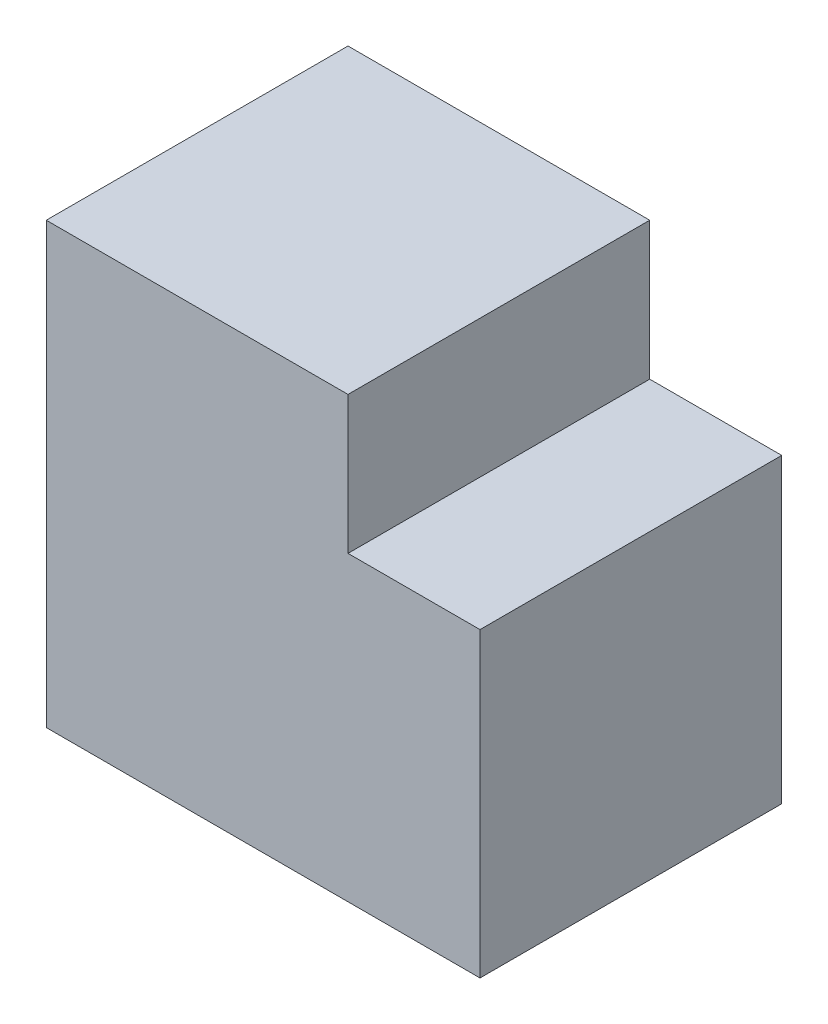
SolidWorks part; units mm, degrees
ref_plane "Front Plane" through (0, 0, 0) normal (0, 0, 1) x (1, 0, 0)
ref_plane "Top Plane" through (0, 0, 0) normal (0, 1, 0) x (1, 0, 0)
ref_plane "Right Plane" through (0, 0, 0) normal (1, 0, 0) x (0, 0, -1)
sketch "Sketch1" plane through (0, 0, 0) normal (0, 1, 0) x (1, 0, 0)
  line L1 (-39.3028, 26.5568) -> (1.3372, 26.5568)
  line L2 (-39.3028, 26.5568) -> (-39.3028, -14.0832)
  line L3 (-39.3028, -14.0832) -> (1.3372, -14.0832)
  line L4 (1.3372, 26.5568) -> (1.3372, -14.0832)
  line L5 (-39.3028, 26.5568) -> (1.3372, -14.0832) construction
  line L6 (-39.3028, -14.0832) -> (1.3372, 26.5568) construction
  point P0 (-18.9828, 6.2368)
  dimension "D1" = 40.64
  dimension "D2" = 40.64
extrude "Boss-Extrude1" add sketch "Sketch1" along normal blind 59.182
sketch "Sketch2" plane through (1.3372, 0, 0) normal (1, 0, 0) x (0, 0, -1)
  line L0 (-14.0832, 40.64) -> (26.5568, 40.64) construction
  line L1 (-14.0832, 59.182) -> (-14.0832, 0) construction
  line L2 (26.5568, 59.182) -> (26.5568, 0) construction
  line L3 (-14.0832, 0) -> (26.5568, 0) construction
  line L5 (-14.0832, 40.64) -> (26.5568, 40.64)
  line L6 (-14.0832, 40.64) -> (-14.0832, 0)
  line L7 (-14.0832, 0) -> (26.5568, 0)
  line L8 (26.5568, 40.64) -> (26.5568, 0)
  dimension "D1" = 40.64
extrude "Boss-Extrude2" add sketch "Sketch2" along normal blind 17.78
sketch "Sketch3" plane through (0, 59.182, 0) normal (0, 1, 0) x (1, 0, 0)
  line L0 (-39.3028, -14.0832) -> (1.3372, 26.5568) construction
  line L1 (1.3372, 26.5568) -> (-39.3028, 26.5568) construction
  line L2 (-2.2188, -10.5272) -> (-35.7468, -10.5272)
  line L3 (-2.2188, -10.5272) -> (-2.2188, 23.0008)
  line L4 (-2.2188, 23.0008) -> (-35.7468, 23.0008)
  line L5 (-35.7468, -10.5272) -> (-35.7468, 23.0008)
  line L6 (-2.2188, -10.5272) -> (-35.7468, 23.0008) construction
  line L7 (-2.2188, 23.0008) -> (-35.7468, -10.5272) construction
  line L8 (1.3372, -14.0832) -> (1.3372, 26.5568) construction
  point P4 (-18.9828, 6.2368)
  dimension "D1" = 3.556
  dimension "D2" = 3.556
shell "Shell1" thickness 2.54
